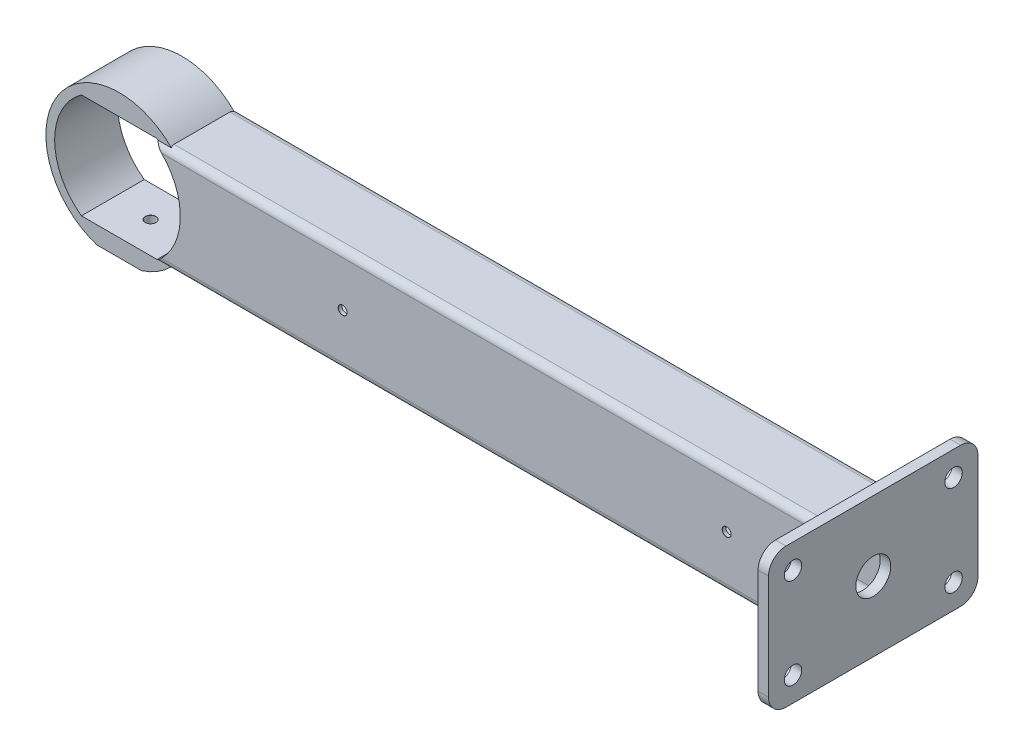
SolidWorks part; units mm, degrees
material "1.0503 (C45)"
ref_plane "Front Plane" through (0, 0, 0) normal (0, 0, 1) x (1, 0, 0)
ref_plane "Top Plane" through (0, 0, 0) normal (0, 1, 0) x (1, 0, 0)
ref_plane "Right Plane" through (0, 0, 0) normal (1, 0, 0) x (0, 0, -1)
sketch "Sketch2" plane through (0, 0, 0) normal (1, 0, 0) x (0, 0, -1)
  line L1 (-7, 14) -> (7, 14)
  line L2 (-9, 12) -> (-9, -12)
  line L3 (-7, -14) -> (7, -14)
  line L4 (9, 12) -> (9, -12)
  line L5 (-9, 14) -> (9, -14) construction
  line L6 (-9, -14) -> (9, 14) construction
  line L7 (-8, 15) -> (8, 15)
  line L8 (-10, 13) -> (-10, -13)
  line L9 (-8, -15) -> (8, -15)
  line L10 (10, 13) -> (10, -13)
  line L11 (-10, 15) -> (10, -15) construction
  line L12 (-10, -15) -> (10, 15) construction
  arc A0 (8, 15) -> (10, 13) centre (8, 13) cw
  arc A1 (-8, 15) -> (-10, 13) centre (-8, 13) ccw
  arc A2 (-8, -15) -> (-10, -13) centre (-8, -13) cw
  arc A3 (8, -15) -> (10, -13) centre (8, -13) ccw
  arc A4 (9, -12) -> (7, -14) centre (7, -12) cw
  arc A5 (-7, -14) -> (-9, -12) centre (-7, -12) cw
  arc A6 (-9, 12) -> (-7, 14) centre (-7, 12) cw
  arc A7 (7, 14) -> (9, 12) centre (7, 12) cw
  point P0 (0, 0)
  point P1 (0, 0)
  point P7 (0, 0)
  dimension "D5" = 2
  dimension "D1" = 30
  dimension "D2" = 20
  dimension "D3" = 18
  dimension "D4" = 28
extrude "Boss-Extrude1" add sketch "Sketch2" along normal blind 207
ref_plane "Sketch8" through (207, 0, 0) normal (1, 0, 0) x (0, 0, -1)
sketch "Sketch9" plane through (207, 0, 0) normal (1, 0, 0) x (0, 0, -1)
  line L1 (-30, -20) -> (30, -20)
  line L2 (0, -20) -> (0, 20)
  line L3 (-30, 20) -> (30, 20)
  line L4 (30, -20) -> (30, 20)
  line L5 (0, 0) -> (41.0566, 0) construction
  line L6 (23, 40.0805) -> (23, -47.0797) construction
  line L7 (-30, -20) -> (-30, 20)
  circle A0 centre (23, 13) radius 2.5
  circle A1 centre (23, -13) radius 2.5
  circle A2 centre (0, 0) radius 5
  circle A3 centre (-23, -13) radius 2.5
  circle A4 centre (-23, 13) radius 2.5
  point P9 (23, 0)
  point P12 (23, 0)
  point P13 (23, 13)
  point P14 (23, -13)
  dimension "D3" = 30
  dimension "D4" = 23
  dimension "D5" = 13
  dimension "D6" = 13
extrude "Boss-Extrude2" add sketch "Sketch9" against normal blind 3 contours A2 L2 L1 L4 L3 A1 A0 | A2 L2 L3 L7 L1 A3 A4 region at (207, 0, 15.1708) region at (207, 0, -15.1708)
sketch "Sketch10" plane through (0, 0, 0) normal (0, 0, 1) x (1, 0, 0)
  line L1 (0, 13) -> (0, -13) construction
  line L2 (0, 0) -> (0, 19.4509) construction
  line L3 (0, 19.4509) -> (0, -17.2685) construction
  line L4 (10.8282, -15) -> (-10.8282, -15)
  line L5 (10.8282, 15) -> (-10.8282, 15)
  circle A0 centre (0, 0) radius 21
  circle A1 centre (0, 0) radius 18.5
  point P0 (0, 0)
  point P6 (0, 15)
  point P10 (0, -15)
  dimension "D1" = 42
  dimension "D2" = 37
  dimension "D3" = 15
  dimension "D4" = 15
extrude "Boss-Extrude3" add sketch "Sketch10" along normal blind 9 and the other way blind 9 contours L5 A1 | A0 A1 | L4 A1 region at (0, -16.412, 0) region at (0, 16.412, 0) region at (-20.406, 0, 0)
extrude "Cut-Extrude1" cut sketch "Sketch10<3>" against normal blind 19 and the other way blind 19 contours L5 A1 L4 region at (0, 0, 0)
sketch "Sketch10<3>" plane through (0, 0, 0) normal (0, 0, 1) x (1, 0, 0) same geometry as "Sketch10"
hole_wizard "Ø3.0mm Dowel Hole1" positions "Sketch11" profile "Sketch12" hole size "Ø3.0" standard "ISO"
sketch "Sketch11" plane through (0, -15, 0) normal (0, 1, 0) x (1, 0, 0)
  point P0 (0, 0)
sketch "Sketch12" plane through (0, -15, 0) normal (1, 0, 0) x (0, 0, 1)
  line L0 (0, 0) -> (0, 8.4013)
  line L1 (0, 8.4013) -> (1.5, 7.5)
  line L2 (1.5, 7.5) -> (1.5, 0.025)
  line L3 (1.5, 0.025) -> (1.525, 0)
  line L5 (1.525, 0) -> (0, 0)
  line L6 (-1.5, 0.025) -> (-1.525, 0) construction
  line L10 (0, 8.4013) -> (-1.5, 7.5) construction
  line L11 (0, -6.35) -> (0, 107.95) construction
  dimension "Hole Dia." = 3
  dimension "Hole Depth" = 7.5
  dimension "Near C'Sink Dia." = 3.05
  dimension "Near C'Sink Angle" = 90
  dimension "Drill Angle" = 118
fillet "Fillet1" radius 5 4 edges at (205.5, 20, 30) (205.5, -20, 30) (205.5, -20, -30) (205.5, 20, -30)
ref_plane "Plane1" through (0, -20, 0) normal (0, 1, 0) x (1, 0, 0)
sketch "Sketch13" plane through (0, -20, 0) normal (0, 1, 0) x (1, 0, 0)
  line L1 (-9.9126, -9.836) -> (9.9126, -9.836)
  line L2 (-9.9126, -9.836) -> (-9.9126, 9.836)
  line L3 (-9.9126, 9.836) -> (9.9126, 9.836)
  line L4 (9.9126, -9.836) -> (9.9126, 9.836)
  line L5 (-9.9126, -9.836) -> (9.9126, 9.836) construction
  line L6 (-9.9126, 9.836) -> (9.9126, -9.836) construction
  point P0 (0, 0)
extrude "Cut-Extrude2" cut sketch "Sketch13" against normal blind 10
ref_plane "Plane2" through (0, 0, 10) normal (0, 0, 1) x (1, 0, 0)
sketch "Sketch14" plane through (0, 0, 10) normal (0, 0, 1) x (1, 0, 0)
  line L0 (0, 0) -> (315.7636, 0) construction
  line L1 (105, 0) -> (105, -51.5188) construction
  line L2 (105, 0) -> (105, 53.7889) construction
  line L3 (245, 0) -> (245, 40.0545) construction
  line L4 (245, 0) -> (245, -47.2258) construction
  line L6 (60.15, -5) -> (69.85, -5)
  line L7 (60.15, -5) -> (60.15, 5)
  line L8 (60.15, 5) -> (69.85, 5)
  line L9 (69.85, -5) -> (69.85, 5)
  line L10 (60.15, -5) -> (69.85, 5) construction
  line L11 (60.15, 5) -> (69.85, -5) construction
  line L13 (179.85, -5) -> (170.15, -5)
  line L14 (179.85, -5) -> (179.85, 5)
  line L15 (179.85, 5) -> (170.15, 5)
  line L16 (170.15, -5) -> (170.15, 5)
  line L17 (179.85, -5) -> (170.15, 5) construction
  line L18 (179.85, 5) -> (170.15, -5) construction
  circle A0 centre (65, 0) radius 4
  circle A1 centre (65, 0) radius 2
  circle A2 centre (175, 0) radius 4
  circle A3 centre (175, 0) radius 2
  point P3 (105, 0)
  point P4 (245, 0)
  point P10 (245, -25)
  point P12 (245, 25)
  point P13 (105, 34)
  point P14 (105, -34)
  point P15 (65, 0)
  point P16 (175, 0)
  point P18 (65, 0)
  point P24 (175, 0)
  dimension "D1" = 105
  dimension "D2" = 245
  dimension "D3" = 34
  dimension "D4" = 34
  dimension "D5" = 25
  dimension "D6" = 25
  dimension "D7" = 65
  dimension "D8" = 315.7636
  dimension "D9" = 175
  dimension "D10" = 10
  dimension "D11" = 10
hole_wizard "Ø2.5mm Dowel Hole1" positions "Sketch15" profile "Sketch16" hole size "Ø2.5" standard "KS" end condition through all
sketch "Sketch15" plane through (0, 0, 10) normal (0, 0, 1) x (1, 0, 0)
  point P0 (65, 0)
  point P3 (175, 0)
sketch "Sketch16" plane through (65, 0, 10) normal (1, 0, 0) x (0, -1, 0)
  line L0 (0, 0) -> (0, 40)
  line L1 (0, 40) -> (1.25, 40)
  line L2 (1.25, 40) -> (1.25, 0.025)
  line L3 (1.25, 0.025) -> (1.275, 0)
  line L5 (1.275, 0) -> (0, 0)
  line L6 (-1.25, 0.025) -> (-1.275, 0) construction
  line L11 (0, -6.35) -> (0, 107.95) construction
  dimension "Thru Hole Dia." = 2.5
  dimension "Thru Hole Depth" = 40
  dimension "Near C'Sink Dia." = 2.55
  dimension "Near C'Sink Angle" = 90
